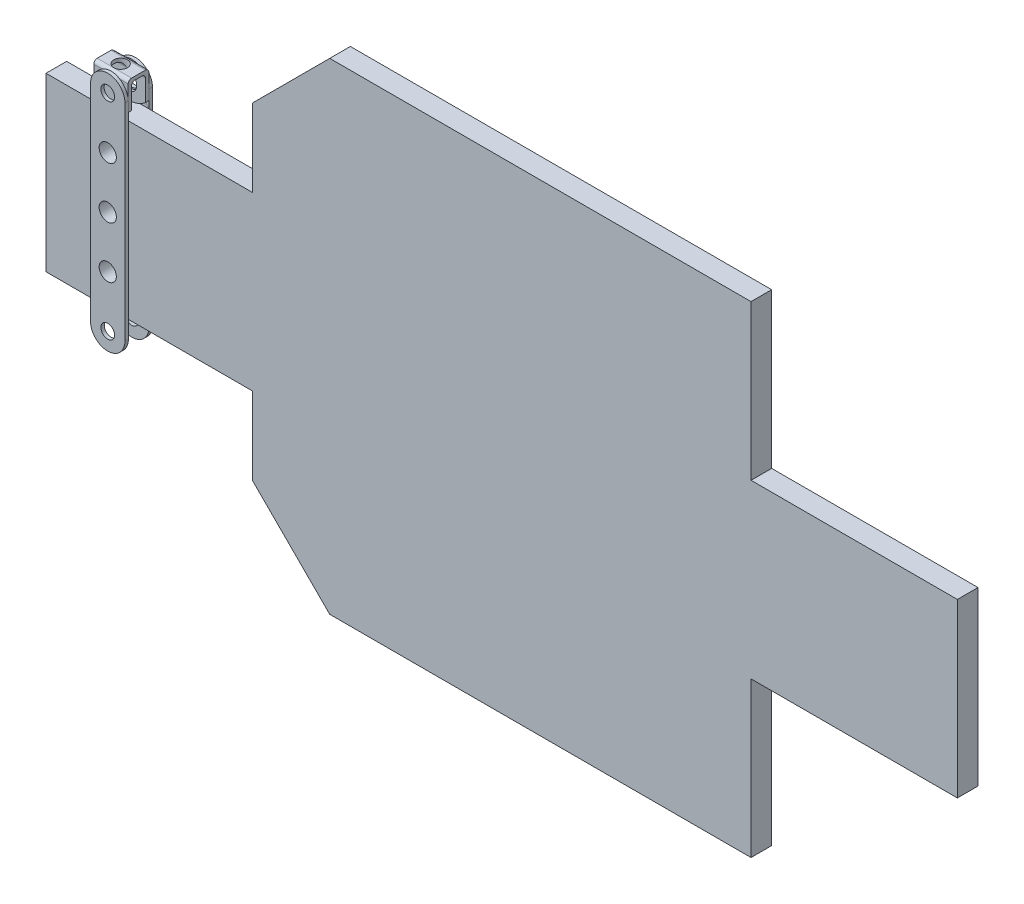
SolidWorks part; units mm, degrees
note: The reader was unsure of these and kept them because the rebuilt part matched: shared geometry of "Эскиз4<2>", "Эскиз7<2>", "Эскиз12<2>", "Эскиз12<3>", "Эскиз15<6>".
ref_plane "Спереди" through (0, 0, 0) normal (0, 0, 1) x (1, 0, 0)
ref_plane "Сверху" through (0, 0, 0) normal (0, 1, 0) x (1, 0, 0)
ref_plane "Справа" through (0, 0, 0) normal (1, 0, 0) x (0, 0, -1)
sketch "Эскиз4" plane through (0, 0, 0) normal (0, 0, 1) x (1, 0, 0)
  line L0 (0, 0) -> (0, 50)
  line L1 (0, 50) -> (60, 50)
  line L2 (60, 50) -> (60, 72.5)
  line L3 (82.5, 95) -> (205, 95)
  line L4 (205, 95) -> (205, 50)
  line L5 (205, 50) -> (265, 50)
  line L6 (205, 0) -> (265, 0)
  line L8 (205, 0) -> (205, -45)
  line L9 (60, 0) -> (60, -22.5)
  line L10 (82.5, -45) -> (205, -45)
  line L11 (60, 0) -> (0, 0)
  line L12 (60, 72.5) -> (82.5, 95)
  line L13 (60, -22.5) -> (82.5, -45)
  line L14 (265, 50) -> (265, 0)
  point P18 (60, -22.5)
  point P19 (82.5, -45)
  dimension "D1" = 140
  dimension "D2" = 122.5
  dimension "D3" = 22.5
  dimension "D4" = 122.5
  dimension "D5" = 265
  dimension "D6" = 45
  dimension "D7" = 50
  dimension "D8" = 22.5
  dimension "D9" = 22.5
  dimension "D10" = 60
  dimension "D11" = 60
surface "Поверхность-Плоскость1" sketch "Эскиз4"
extrude "Бобышка-Вытянуть2" add sketch "Эскиз4<2>" along normal blind 6 contours L12 L3 L4 L5 L14 L6 L8 L10 L13 L9 L11 L0 L1 L2
sketch "Эскиз4<2>" plane through (0, 0, 0) normal (0, 0, 1) x (1, 0, 0) same geometry as "Эскиз4"
sketch "Эскиз7" plane through (0, 0, 0) normal (0, 0, 1) x (1, 0, 0)
  line L0 (13.95, 55) -> (13.95, -5)
  line L2 (23.95, 55) -> (23.95, -5)
  arc A0 (13.95, 55) -> (23.95, 55) centre (18.95, 55) cw
  arc A1 (13.95, -5) -> (23.95, -5) centre (18.95, -5) ccw
  circle A2 centre (18.95, 55) radius 2
  circle A3 centre (18.95, -5) radius 2
  circle A4 centre (18.95, 40) radius 2.5
  circle A5 centre (18.95, 10) radius 2.5
  circle A6 centre (18.95, 25) radius 2.5
  point P14 (18.95, 60)
  dimension "D1" = 60
  dimension "D2" = 4
  dimension "D3" = 5
surface "Поверхность-Плоскость2" sketch "Эскиз7"
extrude "Бобышка-Вытянуть3" add sketch "Эскиз7<2>" against normal blind 1 contours A0 L2 A1 L0
sketch "Эскиз7<2>" plane through (0, 0, 0) normal (0, 0, 1) x (1, 0, 0) same geometry as "Эскиз7"
pattern_linear "Линейный массив1" count 2 spacing 7 along (0, 0, 1) of "Бобышка-Вытянуть3"
sketch "Эскиз12" plane through (0, 0, 0) normal (0, 0, 1) x (1, 0, 0)
  circle A0 centre (18.95, 55) radius 2
  circle A1 centre (18.95, 40) radius 2.5
  circle A2 centre (18.95, 25) radius 2.5
  circle A3 centre (18.95, 10) radius 2.5
  circle A4 centre (18.95, -5) radius 2
surface "Поверхность-Плоскость3" sketch "Эскиз12"
extrude "Вырез-Вытянуть2" cut sketch "Эскиз12<2>" along normal blind 31 contours A0 | A2 | A3 | A4 | A1
sketch "Эскиз12<2>" plane through (0, 0, 0) normal (0, 0, 1) x (1, 0, 0) same geometry as "Эскиз12"
extrude "Вырез-Вытянуть3" cut sketch "Эскиз12<3>" against normal blind 31 contours A4 | A3 | A2 | A1 | A0
sketch "Эскиз12<3>" plane through (0, 0, 0) normal (0, 0, 1) x (1, 0, 0) same geometry as "Эскиз12"
sketch "Эскиз14" plane through (13.95, 61.8554, -9.0804) normal (-1, 0, 0) x (0, 0, 1)
  line L0 (9.1439, -11.5642) -> (9.1439, -6.5642)
  line L1 (9.1439, -11.5642) -> (10.1439, -11.5642)
  line L2 (9.1439, -6.5642) -> (9.1439, -2.5642)
  line L3 (10.1439, -1.5642) -> (14.1439, -1.5642)
  line L4 (15.1439, -2.5642) -> (15.1439, -11.5642)
  line L5 (15.1439, -11.5642) -> (14.1439, -11.5642)
  line L6 (14.1439, -11.5642) -> (14.1439, -3.5642)
  line L7 (11.1439, -2.5642) -> (13.1439, -2.5642)
  line L8 (10.1439, -11.5642) -> (10.1439, -3.5642)
  arc A0 (9.1439, -2.5642) -> (10.1439, -1.5642) centre (10.1439, -2.5642) cw
  arc A1 (14.1439, -1.5642) -> (15.1439, -2.5642) centre (14.1439, -2.5642) cw
  arc A2 (14.1439, -3.5642) -> (13.1439, -2.5642) centre (13.1439, -3.5642) ccw
  arc A3 (10.1439, -3.5642) -> (11.1439, -2.5642) centre (11.1439, -3.5642) cw
extrude "Бобышка-Вытянуть4" add sketch "Эскиз14" along normal blind 0.0001 and the other way blind 10 separate body
sketch "Эскиз15" plane through (13.95, 55.1581, 6.0636) normal (0, 0, 1) x (1, 0, 0)
  circle A0 centre (5, 0) radius 2.5
sketch "Эскиз17" plane through (0, 0, 0) normal (0, 1, 0) x (1, 0, 0)
  circle A0 centre (5, -0.1) radius 2
surface "Поверхность-Плоскость8" sketch "Эскиз15"
extrude "Вырез-Вытянуть21" cut sketch "Эскиз15<6>" against normal blind 30 contours A0
sketch "Эскиз15<6>" plane through (13.95, 55.1581, 6.0636) normal (0, 0, 1) x (1, 0, 0) same geometry as "Эскиз15"
sketch "Эскиз36" plane through (0, 0, 0) normal (0, 0, 1) x (1, 0, 0)
  line L0 (13.95, 50.1188) -> (13.95, 52.1178)
  line L1 (13.95, 55) -> (13.95, -5) construction
  line L2 (23.95, 55) -> (23.95, -5) construction
  line L3 (23.95, 52.1178) -> (23.95, 50.1188)
  line L4 (23.95, 50.1188) -> (13.95, 50.1188)
  line L5 (13.95, 52.1178) -> (13.954, 52.1199)
  arc A0 (13.95, 52.1178) -> (23.95, 52.1178) centre (18.95, 58.0773) ccw
extrude "Вырез-Вытянуть25" cut sketch "Эскиз36" along normal blind 30 contours A0 L3 L4 L0
sketch "Эскиз37" plane through (0, 0, 0) normal (0, 1, 0) x (1, 0, 0)
  circle A0 centre (18.75, -3.05) radius 2
extrude "Вырез-Вытянуть28" cut sketch "Эскиз37" along normal blind 150
